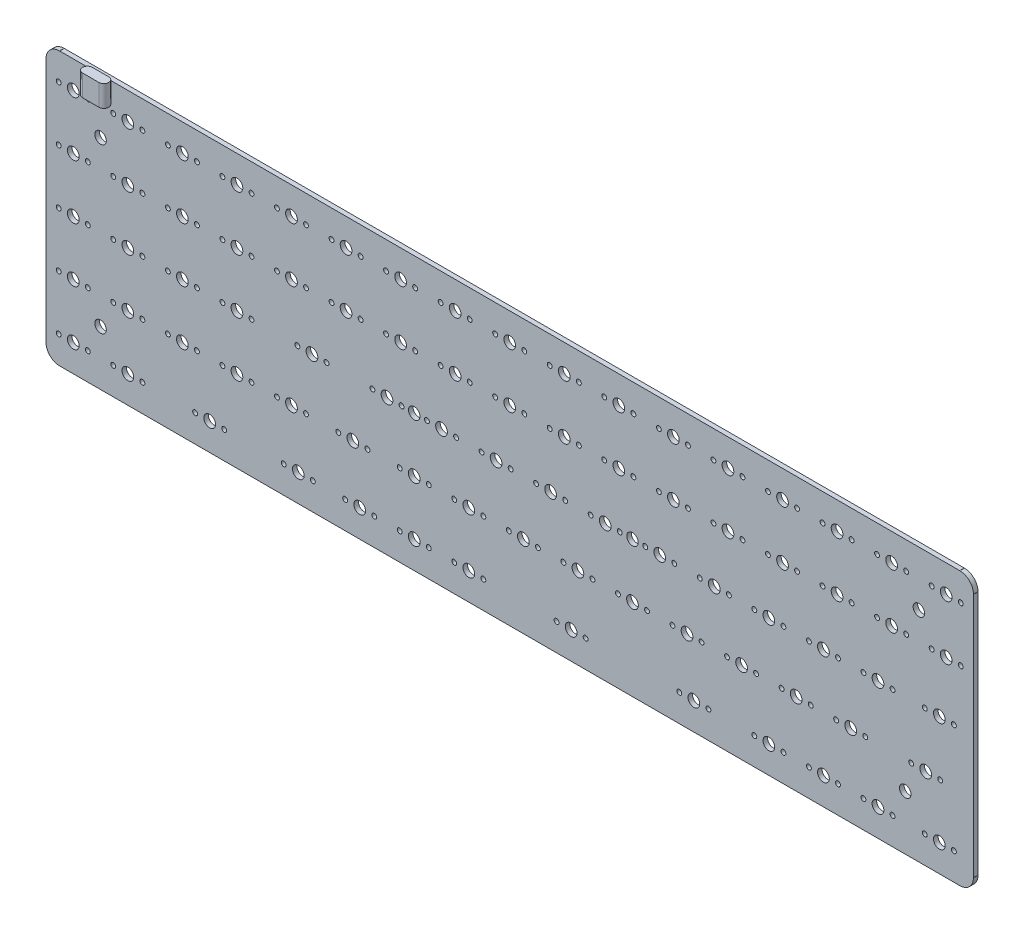
SolidWorks part; units mm, degrees
ref_plane "Front" through (0, 0, 0) normal (0, 0, 1) x (1, 0, 0)
ref_plane "Top" through (0, 0, 0) normal (0, 1, 0) x (1, 0, 0)
ref_plane "Right" through (0, 0, 0) normal (1, 0, 0) x (0, 0, -1)
sketch "Sketch2" plane through (0, 0, 0) normal (0, 0, 1) x (1, 0, 0)
  line L0 (314.325, -4.7625) -> (314.325, 80.9625)
  line L1 (309.5625, 85.725) -> (-4.7625, 85.725)
  line L2 (-9.525, 80.9625) -> (-9.525, -4.7625)
  line L3 (-4.7625, -9.525) -> (309.5625, -9.525)
  arc A0 (314.3631, 80.9625) -> (314.2869, 80.9625) centre (314.325, 80.9625) ccw
  arc A1 (314.2869, -4.7625) -> (314.3631, -4.7625) centre (314.325, -4.7625) ccw
  arc A2 (314.325, 80.9625) -> (309.5625, 85.725) centre (309.5624, 80.9624) ccw
  arc A3 (314.2869, 80.9625) -> (314.3631, 80.9625) centre (314.325, 80.9625) ccw
  arc A4 (309.5625, 85.7631) -> (309.5625, 85.6869) centre (309.5625, 85.725) ccw
  arc A5 (-4.7625, 85.7631) -> (-4.7625, 85.6869) centre (-4.7625, 85.725) ccw
  arc A6 (309.5625, 85.6869) -> (309.5625, 85.7631) centre (309.5625, 85.725) ccw
  arc A7 (-4.7625, 85.725) -> (-9.525, 80.9625) centre (-4.7624, 80.9624) ccw
  arc A8 (-4.7625, 85.6869) -> (-4.7625, 85.7631) centre (-4.7625, 85.725) ccw
  arc A9 (-9.5631, 80.9625) -> (-9.4869, 80.9625) centre (-9.525, 80.9625) ccw
  arc A10 (-9.5631, -4.7625) -> (-9.4869, -4.7625) centre (-9.525, -4.7625) ccw
  arc A11 (-9.4869, 80.9625) -> (-9.5631, 80.9625) centre (-9.525, 80.9625) ccw
  arc A12 (-9.525, -4.7625) -> (-4.7625, -9.525) centre (-4.7624, -4.7624) ccw
  arc A13 (-9.4869, -4.7625) -> (-9.5631, -4.7625) centre (-9.525, -4.7625) ccw
  arc A14 (-4.7625, -9.5631) -> (-4.7625, -9.4869) centre (-4.7625, -9.525) ccw
  arc A15 (309.5625, -9.5631) -> (309.5625, -9.4869) centre (309.5625, -9.525) ccw
  arc A16 (-4.7625, -9.4869) -> (-4.7625, -9.5631) centre (-4.7625, -9.525) ccw
  arc A17 (309.5625, -9.525) -> (314.325, -4.7625) centre (309.5624, -4.7624) ccw
  arc A18 (309.5625, -9.4869) -> (309.5625, -9.5631) centre (309.5625, -9.525) ccw
  arc A19 (314.3631, -4.7625) -> (314.2869, -4.7625) centre (314.325, -4.7625) ccw
  circle A20 centre (9.525, 66.675) radius 2
  circle A21 centre (9.525, 9.525) radius 2
  circle A22 centre (295.275, 66.675) radius 2
  circle A23 centre (290.5125, 9.525) radius 2
  circle A24 centre (119.0625, 38.1) radius 2
  circle A25 centre (195.2625, 38.1) radius 2
  circle A26 centre (304.8, 76.2) radius 2.0447
  circle A27 centre (299.72, 76.2) radius 0.8534
  circle A28 centre (309.88, 76.2) radius 0.8534
  circle A29 centre (285.75, 76.2) radius 2.0447
  circle A30 centre (280.67, 76.2) radius 0.8534
  circle A31 centre (290.83, 76.2) radius 0.8534
  circle A32 centre (266.7, 76.2) radius 2.0447
  circle A33 centre (261.62, 76.2) radius 0.8534
  circle A34 centre (271.78, 76.2) radius 0.8534
  circle A35 centre (247.65, 76.2) radius 2.0447
  circle A36 centre (242.57, 76.2) radius 0.8534
  circle A37 centre (252.73, 76.2) radius 0.8534
  circle A38 centre (228.6, 76.2) radius 2.0447
  circle A39 centre (223.52, 76.2) radius 0.8534
  circle A40 centre (233.68, 76.2) radius 0.8534
  circle A41 centre (209.55, 76.2) radius 2.0447
  circle A42 centre (204.47, 76.2) radius 0.8534
  circle A43 centre (214.63, 76.2) radius 0.8534
  circle A44 centre (190.5, 76.2) radius 2.0447
  circle A45 centre (185.42, 76.2) radius 0.8534
  circle A46 centre (195.58, 76.2) radius 0.8534
  circle A47 centre (171.45, 76.2) radius 2.0447
  circle A48 centre (166.37, 76.2) radius 0.8534
  circle A49 centre (176.53, 76.2) radius 0.8534
  circle A50 centre (152.4, 76.2) radius 2.0447
  circle A51 centre (147.32, 76.2) radius 0.8534
  circle A52 centre (157.48, 76.2) radius 0.8534
  circle A53 centre (133.35, 76.2) radius 2.0447
  circle A54 centre (128.27, 76.2) radius 0.8534
  circle A55 centre (138.43, 76.2) radius 0.8534
  circle A56 centre (114.3, 76.2) radius 2.0447
  circle A57 centre (109.22, 76.2) radius 0.8534
  circle A58 centre (119.38, 76.2) radius 0.8534
  circle A59 centre (95.25, 76.2) radius 2.0447
  circle A60 centre (90.17, 76.2) radius 0.8534
  circle A61 centre (100.33, 76.2) radius 0.8534
  circle A62 centre (76.2, 76.2) radius 2.0447
  circle A63 centre (71.12, 76.2) radius 0.8534
  circle A64 centre (81.28, 76.2) radius 0.8534
  circle A65 centre (57.15, 76.2) radius 2.0447
  circle A66 centre (52.07, 76.2) radius 0.8534
  circle A67 centre (62.23, 76.2) radius 0.8534
  circle A68 centre (38.1, 76.2) radius 2.0447
  circle A69 centre (33.02, 76.2) radius 0.8534
  circle A70 centre (43.18, 76.2) radius 0.8534
  circle A71 centre (19.05, 76.2) radius 2.0447
  circle A72 centre (13.97, 76.2) radius 0.8534
  circle A73 centre (24.13, 76.2) radius 0.8534
  circle A74 centre (0, 76.2) radius 2.0447
  circle A75 centre (-5.08, 76.2) radius 0.8534
  circle A76 centre (5.08, 76.2) radius 0.8534
  circle A77 centre (304.8, 57.15) radius 2.0447
  circle A78 centre (299.72, 57.15) radius 0.8534
  circle A79 centre (309.88, 57.15) radius 0.8534
  circle A80 centre (285.75, 57.15) radius 2.0447
  circle A81 centre (280.67, 57.15) radius 0.8534
  circle A82 centre (290.83, 57.15) radius 0.8534
  circle A83 centre (266.7, 57.15) radius 2.0447
  circle A84 centre (261.62, 57.15) radius 0.8534
  circle A85 centre (271.78, 57.15) radius 0.8534
  circle A86 centre (247.65, 57.15) radius 2.0447
  circle A87 centre (242.57, 57.15) radius 0.8534
  circle A88 centre (252.73, 57.15) radius 0.8534
  circle A89 centre (228.6, 57.15) radius 2.0447
  circle A90 centre (223.52, 57.15) radius 0.8534
  circle A91 centre (233.68, 57.15) radius 0.8534
  circle A92 centre (209.55, 57.15) radius 2.0447
  circle A93 centre (204.47, 57.15) radius 0.8534
  circle A94 centre (214.63, 57.15) radius 0.8534
  circle A95 centre (190.5, 57.15) radius 2.0447
  circle A96 centre (185.42, 57.15) radius 0.8534
  circle A97 centre (195.58, 57.15) radius 0.8534
  circle A98 centre (171.45, 57.15) radius 2.0447
  circle A99 centre (166.37, 57.15) radius 0.8534
  circle A100 centre (176.53, 57.15) radius 0.8534
  circle A101 centre (152.4, 57.15) radius 2.0447
  circle A102 centre (147.32, 57.15) radius 0.8534
  circle A103 centre (157.48, 57.15) radius 0.8534
  circle A104 centre (133.35, 57.15) radius 2.0447
  circle A105 centre (128.27, 57.15) radius 0.8534
  circle A106 centre (138.43, 57.15) radius 0.8534
  circle A107 centre (114.3, 57.15) radius 2.0447
  circle A108 centre (109.22, 57.15) radius 0.8534
  circle A109 centre (119.38, 57.15) radius 0.8534
  circle A110 centre (95.25, 57.15) radius 2.0447
  circle A111 centre (90.17, 57.15) radius 0.8534
  circle A112 centre (100.33, 57.15) radius 0.8534
  circle A113 centre (76.2, 57.15) radius 2.0447
  circle A114 centre (71.12, 57.15) radius 0.8534
  circle A115 centre (81.28, 57.15) radius 0.8534
  circle A116 centre (57.15, 57.15) radius 2.0447
  circle A117 centre (52.07, 57.15) radius 0.8534
  circle A118 centre (62.23, 57.15) radius 0.8534
  circle A119 centre (38.1, 57.15) radius 2.0447
  circle A120 centre (33.02, 57.15) radius 0.8534
  circle A121 centre (43.18, 57.15) radius 0.8534
  circle A122 centre (19.05, 57.15) radius 2.0447
  circle A123 centre (13.97, 57.15) radius 0.8534
  circle A124 centre (24.13, 57.15) radius 0.8534
  circle A125 centre (0, 57.15) radius 2.0447
  circle A126 centre (-5.08, 57.15) radius 0.8534
  circle A127 centre (5.08, 57.15) radius 0.8534
  circle A128 centre (302.4187, 38.1) radius 2.0447
  circle A129 centre (297.3388, 38.1) radius 0.8534
  circle A130 centre (307.4988, 38.1) radius 0.8534
  circle A131 centre (280.9875, 38.1) radius 2.0447
  circle A132 centre (275.9075, 38.1) radius 0.8534
  circle A133 centre (286.0675, 38.1) radius 0.8534
  circle A134 centre (261.9375, 38.1) radius 2.0447
  circle A135 centre (256.8575, 38.1) radius 0.8534
  circle A136 centre (267.0175, 38.1) radius 0.8534
  circle A137 centre (242.8875, 38.1) radius 2.0447
  circle A138 centre (237.8075, 38.1) radius 0.8534
  circle A139 centre (247.9675, 38.1) radius 0.8534
  circle A140 centre (223.8375, 38.1) radius 2.0447
  circle A141 centre (218.7575, 38.1) radius 0.8534
  circle A142 centre (228.9175, 38.1) radius 0.8534
  circle A143 centre (204.7875, 38.1) radius 2.0447
  circle A144 centre (199.7075, 38.1) radius 0.8534
  circle A145 centre (209.8675, 38.1) radius 0.8534
  circle A146 centre (185.7375, 38.1) radius 2.0447
  circle A147 centre (180.6575, 38.1) radius 0.8534
  circle A148 centre (190.8175, 38.1) radius 0.8534
  circle A149 centre (166.6875, 38.1) radius 2.0447
  circle A150 centre (161.6075, 38.1) radius 0.8534
  circle A151 centre (171.7675, 38.1) radius 0.8534
  circle A152 centre (147.6375, 38.1) radius 2.0447
  circle A153 centre (142.5575, 38.1) radius 0.8534
  circle A154 centre (152.7175, 38.1) radius 0.8534
  circle A155 centre (128.5875, 38.1) radius 2.0447
  circle A156 centre (123.5075, 38.1) radius 0.8534
  circle A157 centre (133.6675, 38.1) radius 0.8534
  circle A158 centre (109.5375, 38.1) radius 2.0447
  circle A159 centre (104.4575, 38.1) radius 0.8534
  circle A160 centre (114.6175, 38.1) radius 0.8534
  circle A161 centre (83.3438, 38.1) radius 2.0447
  circle A162 centre (78.2638, 38.1) radius 0.8534
  circle A163 centre (88.4237, 38.1) radius 0.8534
  circle A164 centre (57.15, 38.1) radius 2.0447
  circle A165 centre (52.07, 38.1) radius 0.8534
  circle A166 centre (62.23, 38.1) radius 0.8534
  circle A167 centre (38.1, 38.1) radius 2.0447
  circle A168 centre (33.02, 38.1) radius 0.8534
  circle A169 centre (43.18, 38.1) radius 0.8534
  circle A170 centre (19.05, 38.1) radius 2.0447
  circle A171 centre (13.97, 38.1) radius 0.8534
  circle A172 centre (24.13, 38.1) radius 0.8534
  circle A173 centre (0, 38.1) radius 2.0447
  circle A174 centre (-5.08, 38.1) radius 0.8534
  circle A175 centre (5.08, 38.1) radius 0.8534
  circle A176 centre (297.6563, 19.05) radius 2.0447
  circle A177 centre (292.5763, 19.05) radius 0.8534
  circle A178 centre (302.7363, 19.05) radius 0.8534
  circle A179 centre (271.4625, 19.05) radius 2.0447
  circle A180 centre (266.3825, 19.05) radius 0.8534
  circle A181 centre (276.5425, 19.05) radius 0.8534
  circle A182 centre (252.4125, 19.05) radius 2.0447
  circle A183 centre (247.3325, 19.05) radius 0.8534
  circle A184 centre (257.4925, 19.05) radius 0.8534
  circle A185 centre (233.3625, 19.05) radius 2.0447
  circle A186 centre (228.2825, 19.05) radius 0.8534
  circle A187 centre (238.4425, 19.05) radius 0.8534
  circle A188 centre (214.3125, 19.05) radius 2.0447
  circle A189 centre (209.2325, 19.05) radius 0.8534
  circle A190 centre (219.3925, 19.05) radius 0.8534
  circle A191 centre (195.2625, 19.05) radius 2.0447
  circle A192 centre (190.1825, 19.05) radius 0.8534
  circle A193 centre (200.3425, 19.05) radius 0.8534
  circle A194 centre (176.2125, 19.05) radius 2.0447
  circle A195 centre (171.1325, 19.05) radius 0.8534
  circle A196 centre (181.2925, 19.05) radius 0.8534
  circle A197 centre (157.1625, 19.05) radius 2.0447
  circle A198 centre (152.0825, 19.05) radius 0.8534
  circle A199 centre (162.2425, 19.05) radius 0.8534
  circle A200 centre (138.1125, 19.05) radius 2.0447
  circle A201 centre (133.0325, 19.05) radius 0.8534
  circle A202 centre (143.1925, 19.05) radius 0.8534
  circle A203 centre (119.0625, 19.05) radius 2.0447
  circle A204 centre (113.9825, 19.05) radius 0.8534
  circle A205 centre (124.1425, 19.05) radius 0.8534
  circle A206 centre (97.6313, 19.05) radius 2.0447
  circle A207 centre (92.5513, 19.05) radius 0.8534
  circle A208 centre (102.7113, 19.05) radius 0.8534
  circle A209 centre (76.2, 19.05) radius 2.0447
  circle A210 centre (71.12, 19.05) radius 0.8534
  circle A211 centre (81.28, 19.05) radius 0.8534
  circle A212 centre (57.15, 19.05) radius 2.0447
  circle A213 centre (52.07, 19.05) radius 0.8534
  circle A214 centre (62.23, 19.05) radius 0.8534
  circle A215 centre (38.1, 19.05) radius 2.0447
  circle A216 centre (33.02, 19.05) radius 0.8534
  circle A217 centre (43.18, 19.05) radius 0.8534
  circle A218 centre (19.05, 19.05) radius 2.0447
  circle A219 centre (13.97, 19.05) radius 0.8534
  circle A220 centre (24.13, 19.05) radius 0.8534
  circle A221 centre (0, 19.05) radius 2.0447
  circle A222 centre (-5.08, 19.05) radius 0.8534
  circle A223 centre (5.08, 19.05) radius 0.8534
  circle A224 centre (302.4187, 0) radius 2.0447
  circle A225 centre (297.3388, 0) radius 0.8534
  circle A226 centre (307.4988, 0) radius 0.8534
  circle A227 centre (280.9875, 0) radius 2.0447
  circle A228 centre (275.9075, 0) radius 0.8534
  circle A229 centre (286.0675, 0) radius 0.8534
  circle A230 centre (261.9375, 0) radius 2.0447
  circle A231 centre (256.8575, 0) radius 0.8534
  circle A232 centre (267.0175, 0) radius 0.8534
  circle A233 centre (242.8875, 0) radius 2.0447
  circle A234 centre (237.8075, 0) radius 0.8534
  circle A235 centre (247.9675, 0) radius 0.8534
  circle A236 centre (216.6938, 0) radius 2.0447
  circle A237 centre (211.6138, 0) radius 0.8534
  circle A238 centre (221.7738, 0) radius 0.8534
  circle A239 centre (173.8313, 0) radius 2.0447
  circle A240 centre (168.7512, 0) radius 0.8534
  circle A241 centre (178.9112, 0) radius 0.8534
  circle A242 centre (138.1125, 0) radius 2.0447
  circle A243 centre (133.0325, 0) radius 0.8534
  circle A244 centre (143.1925, 0) radius 0.8534
  circle A245 centre (119.0625, 0) radius 2.0447
  circle A246 centre (113.9825, 0) radius 0.8534
  circle A247 centre (124.1425, 0) radius 0.8534
  circle A248 centre (100.0125, 0) radius 2.0447
  circle A249 centre (94.9325, 0) radius 0.8534
  circle A250 centre (105.0925, 0) radius 0.8534
  circle A251 centre (78.5812, 0) radius 2.0447
  circle A252 centre (73.5012, 0) radius 0.8534
  circle A253 centre (83.6613, 0) radius 0.8534
  circle A254 centre (47.625, 0) radius 2.0447
  circle A255 centre (42.545, 0) radius 0.8534
  circle A256 centre (52.705, 0) radius 0.8534
  circle A257 centre (19.05, 0) radius 2.0447
  circle A258 centre (13.97, 0) radius 0.8534
  circle A259 centre (24.13, 0) radius 0.8534
  circle A260 centre (0, 0) radius 2.0447
  circle A261 centre (-5.08, 0) radius 0.8534
  circle A262 centre (5.08, 0) radius 0.8534
  circle A263 centre (12.415, 80.6463) radius 0.325
  circle A264 centre (6.635, 80.6463) radius 0.325
extrude "Boss-Extrude3" add sketch "Sketch2" along normal mid plane 1.5875 contours A19 L0 A3 A0 A2 A6 A4 L1 A8 A5 A7 A11 A9 L2 A13 A10 A12 A16 A14 L3 A18 A15 A17 A1 A264 A263 A262 A261 A260 A259 A258 A257 A256 A255 A254 A253 A252 region at (311.9111, -2.3486, 0)
ref_plane "Plane1" through (0, 38.1, 0) normal (0, 1, 0) x (1, 0, 0)
ref_plane "Plane2" through (152.4, 0, 0) normal (1, 0, 0) x (0, 0, -1)
sketch "Sketch3" plane through (0, 85.725, 0) normal (0, 1, 0) x (1, 0, 0)
  line L0 (12.3825, -2.5083) -> (6.6675, -2.5083) construction
  line L1 (12.3825, -4.2228) -> (6.6675, -4.2228)
  line L2 (12.3825, -0.7938) -> (6.6675, -0.7938)
  line L3 (309.5244, -0.7937) -> (-4.7244, -0.7937) construction
  line L4 (12.415, 0) -> (6.635, 0) construction
  line L5 (12.415, -0.7937) -> (12.415, 0.7937) construction
  line L6 (6.635, -0.7937) -> (6.635, 0.7937) construction
  arc A0 (12.3825, -4.2228) -> (12.3825, -0.7938) centre (12.3825, -2.5083) ccw
  arc A1 (6.6675, -0.7938) -> (6.6675, -4.2228) centre (6.6675, -2.5083) ccw
  point P2 (9.525, -2.5082)
  point P7 (9.525, 0)
  dimension "D1" = 9.144
  dimension "D2" = 3.429
extrude "Boss-Extrude4" add sketch "Sketch3" along normal blind 0.762 and the other way blind 6.731
